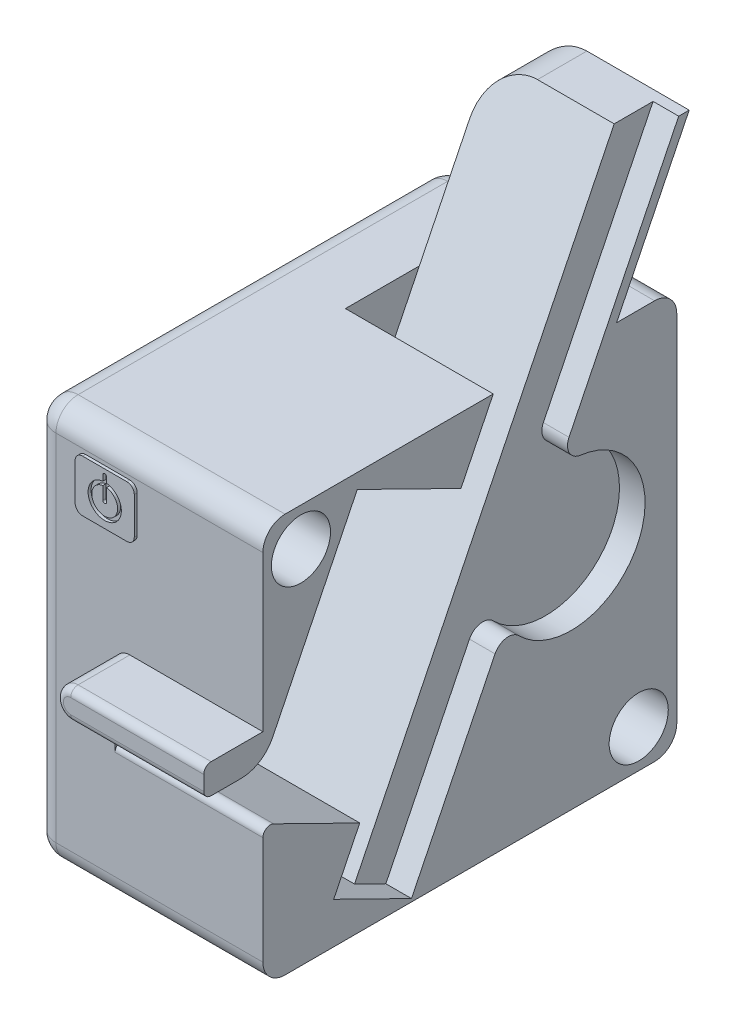
SolidWorks part; units mm, degrees
material "ABS"
ref_plane "Front" through (0, 0, 0) normal (0, 0, 1) x (1, 0, 0)
ref_plane "Top" through (0, 0, 0) normal (0, 1, 0) x (1, 0, 0)
ref_plane "Right" through (0, 0, 0) normal (1, 0, 0) x (0, 0, -1)
sketch "Sketch1" plane through (0, 0, 0) normal (0, 0, 1) x (1, 0, 0)
  line L0 (133.4483, 300.2587) -> (667.2416, 300.2587) construction
  line L2 (-196.85, 342.9) -> (196.85, 342.9)
  line L3 (-196.85, 342.9) -> (-196.85, 0)
  line L4 (-196.85, 0) -> (196.85, 0)
  line L5 (196.85, 342.9) -> (196.85, 0)
  dimension "D1" = 342.9
  dimension "D2" = 393.7
extrude "Boss-Extrude1" add sketch "Sketch1" along normal blind 355.6
sketch "Sketch2" plane through (0, 0, 355.6) normal (0, 0, 1) x (1, 0, 0)
  line L0 (196.85, 342.9) -> (-196.85, 342.9) construction
  line L1 (-158.75, 320.675) -> (-107.95, 320.675)
  line L2 (-158.75, 320.675) -> (-158.75, 276.225)
  line L3 (-158.75, 276.225) -> (-107.95, 276.225)
  line L4 (-107.95, 320.675) -> (-107.95, 276.225)
  line L5 (-158.75, 320.675) -> (-107.95, 276.225) construction
  line L6 (-158.75, 276.225) -> (-107.95, 320.675) construction
  line L7 (-196.85, 342.9) -> (-196.85, 0) construction
  point P0 (-133.35, 298.45)
  dimension "D1" = 44.45
  dimension "D2" = 63.5
  dimension "D3" = 44.45
  dimension "D4" = 50.8
extrude "Boss-Extrude2" add sketch "Sketch2" along normal blind 2.54
sketch "Sketch3" plane through (0, 0, 355.6) normal (0, 0, 1) x (1, 0, 0)
  line L0 (88.9, 298.45) -> (165.1, 298.45) construction
  line L1 (88.9, 307.975) -> (165.1, 307.975)
  line L2 (88.9, 288.925) -> (165.1, 288.925)
  line L5 (-107.95, 298.45) -> (88.9, 298.45) construction
  line L7 (-107.95, 276.225) -> (-107.95, 320.675) construction
  line L8 (196.85, 0) -> (196.85, 342.9) construction
  arc A0 (88.9, 307.975) -> (88.9, 288.925) centre (88.9, 298.45) ccw
  arc A1 (165.1, 288.925) -> (165.1, 307.975) centre (165.1, 298.45) ccw
  point P2 (127, 298.45)
  dimension "D1" = 19.05
  dimension "D2" = 76.2
  dimension "D3" = 31.75
extrude "Boss-Extrude3" add sketch "Sketch3" along normal blind 2.54
sketch "Sketch4" plane through (0, 0, 358.14) normal (0, 0, 1) x (1, 0, 0)
  line L0 (79.375, 298.45) -> (174.625, 298.45) construction
  arc A0 (88.9, 307.975) -> (88.9, 288.925) centre (88.9, 298.45) ccw construction
  arc A1 (165.1, 288.925) -> (165.1, 307.975) centre (165.1, 298.45) ccw construction
  circle A2 centre (92.075, 298.45) radius 3.81
  circle A3 centre (108.2865, 298.45) radius 3.81
  circle A4 centre (124.4979, 298.45) radius 3.81
  dimension "D1" = 7.62
  dimension "D2" = 16.2115
  dimension "D3" = 16.2115
  dimension "D4" = 12.7
extrude "Cut-Extrude1" cut sketch "Sketch4" against normal blind 2.54
sketch "Sketch5" plane through (0, 0, 355.6) normal (0, 0, 1) x (1, 0, 0)
  line L0 (-114.3, 177.8) -> (114.3, 177.8) construction
  line L1 (-114.3, 190.5) -> (114.3, 190.5)
  line L2 (-114.3, 165.1) -> (114.3, 165.1)
  line L3 (0, 177.8) -> (0, 342.9) construction
  line L4 (196.85, 342.9) -> (-196.85, 342.9) construction
  arc A0 (-114.3, 190.5) -> (-114.3, 165.1) centre (-114.3, 177.8) ccw
  arc A1 (114.3, 165.1) -> (114.3, 190.5) centre (114.3, 177.8) ccw
  point P2 (0, 177.8)
  dimension "D1" = 228.6
  dimension "D2" = 25.4
  dimension "D3" = 165.1
extrude "Boss-Extrude4" add sketch "Sketch5" along normal blind 50.8
fillet "Fillet1" radius 6.35 4 edges at (127, 177.8, 406.4) (0, 165.1, 406.4) (-127, 177.8, 406.4) (0, 190.5, 406.4)
fillet "Fillet2" radius 6.35 4 edges at (-158.75, 276.225, 356.87) (-107.95, 276.225, 356.87) (-107.95, 320.675, 356.87) (-158.75, 320.675, 356.87)
sketch "Sketch6" plane through (0, 0, 358.14) normal (0, 0, 1) x (1, 0, 0)
  line L0 (-133.35, 296.545) -> (-133.35, 276.225) construction
  line L3 (-133.35, 296.545) -> (-133.35, 315.595) construction
  line L4 (-134.9375, 296.545) -> (-134.9375, 315.595)
  line L5 (-131.7625, 296.545) -> (-131.7625, 315.595)
  line L6 (-152.4, 276.225) -> (-114.3, 276.225) construction
  circle A1 centre (-133.35, 296.545) radius 11.1125
  circle A2 centre (-133.35, 296.545) radius 14.2875
  arc A3 (-134.9375, 296.545) -> (-131.7625, 296.545) centre (-133.35, 296.545) ccw
  arc A4 (-131.7625, 315.595) -> (-134.9375, 315.595) centre (-133.35, 315.595) ccw
  point P12 (-133.35, 306.07)
  dimension "D2" = 22.225
  dimension "D3" = 3.175
  dimension "D4" = 19.05
  dimension "D5" = 20.32
  dimension "D1" = 3.175
extrude "Cut-Extrude2" cut sketch "Sketch6" against normal blind 2.54 contours L4 A2 L5 A1 | L5 A4 L4 A2 | L5 A2 L4 A1 | L4 A3 L5 A1 region at (-133.35, 301.4538, 358.14) region at (-140.889, 287.8397, 358.14) region at (-133.35, 309.2112, 358.14) region at (-133.35, 313.8328, 358.14)
fillet "Fillet3" radius 19.05 12 edges at (-196.85, 171.45, 0) (-196.85, 171.45, 355.6) (196.85, 171.45, 0) (196.85, 171.45, 355.6) (0, 0, 0) (0, 0, 355.6) (0, 342.9, 0) (0, 342.9, 355.6) (-196.85, 342.9, 177.8) (196.85, 0, 177.8) (-196.85, 0, 177.8) (196.85, 342.9, 177.8)
sketch "Sketch7" plane through (0, 0, 0) normal (1, 0, 0) x (0, 0, -1)
  line L0 (-51.7276, 342.9) -> (10.6627, 469.9)
  line L1 (-336.55, 342.9) -> (-19.05, 342.9) construction
  line L2 (-94.1768, 342.9) -> (-31.7865, 469.9)
  line L3 (-31.7865, 469.9) -> (10.6627, 469.9)
  line L4 (-94.1768, 342.9) -> (-51.7276, 342.9)
  line L5 (0, 323.85) -> (0, 19.05) construction
  dimension "D1" = 38.1
  dimension "D2" = 127
  dimension "D3" = 94.1768
  dimension "D4" = 63.837
extrude "Boss-Extrude5" add sketch "Sketch7" along normal mid plane 254
fillet "Fillet4" radius 39.116 2 edges at (-127, 469.9, 10.5619) (127, 469.9, 10.5619)
sketch "Sketch8" plane through (0, 342.9, 0) normal (0, 1, 0) x (1, 0, 0)
  line L0 (0, -94.1768) -> (0, -125.9268) construction
  line L1 (127, -94.1768) -> (-127, -94.1768) construction
  line L3 (-127, -157.6768) -> (127, -157.6768)
  line L4 (-127, -157.6768) -> (-127, -94.1768)
  line L5 (-127, -94.1768) -> (127, -94.1768)
  line L6 (127, -157.6768) -> (127, -94.1768)
  line L7 (-127, -157.6768) -> (127, -94.1768) construction
  line L8 (-127, -94.1768) -> (127, -157.6768) construction
  dimension "D1" = 63.5
  dimension "D2" = 254
extrude "Cut-Extrude3" cut sketch "Sketch8" against normal blind 25.4
sketch "Sketch9" plane through (0, 0, 0) normal (1, 0, 0) x (0, 0, -1)
  line L1 (-912.7094, 769.4471) -> (-210.006, -1175.153)
  line L2 (-210.006, -1175.153) -> (1122.7154, 405.706)
  line L3 (1122.7154, 405.706) -> (-912.7094, 769.4471)
  circle A0 centre (0, 0) radius 596.8851 construction
extrude "Cut-Extrude4" cut sketch "Sketch9" along normal through all
sketch "Sketch10" plane through (0, 0, 0) normal (1, 0, 0) x (0, 0, -1)
  line L0 (-94.1768, 342.9) -> (-254.8643, 15.8091)
  line L1 (-157.6768, 342.9) -> (-185.414, 286.439)
  line L2 (-31.7865, 469.9) -> (-94.1768, 342.9) construction
  line L3 (-355.6, 165.1) -> (-274.4926, 330.2)
  line L5 (-355.6, 19.05) -> (-355.6, 165.1) construction
  line L7 (-355.6, 165.1) -> (-355.6, 121.8957)
  line L9 (-157.6768, 342.9) -> (-94.1768, 342.9)
  line L14 (-274.4926, 330.2) -> (-185.414, 286.439)
  line L15 (-355.6, 121.8957) -> (-268.5142, 299.1651) construction
  line L16 (-157.6768, 342.9) -> (-336.55, 342.9) construction
  line L17 (-355.6, 121.8957) -> (-272.3609, 81.0035)
  line L19 (-254.8643, 15.8091) -> (-294.7601, 35.4084)
  line L20 (-294.7601, 35.4084) -> (-272.3609, 81.0035)
  dimension "D1" = 19.05
  dimension "D2" = 12.7
  dimension "D3" = 50.8
  dimension "D4" = 44.45
extrude "Cut-Extrude5" cut sketch "Sketch10" against normal blind 127
sketch "Sketch11" plane through (0, 0, 0) normal (1, 0, 0) x (0, 0, -1)
  line L0 (-94.1768, 342.9) -> (-106.6549, 317.5)
  line L1 (-106.6549, 317.5) -> (-94.1768, 317.5)
  line L2 (-94.1768, 317.5) -> (-94.1768, 342.9)
extrude "Boss-Extrude6" add sketch "Sketch11" against normal up to surface (127 mm away) up to face at (-127, 214.2414, 222.3434)
sketch "Sketch12" plane through (0, 103.9367, 211.5706) normal (0, 0.4409, 0.8975) x (1, 0, 0)
  line L0 (-127, -98.1877) -> (0, -98.1877) construction
  line L1 (0, 426.4566) -> (-22, 426.4566)
  line L2 (0, 426.4566) -> (0, -98.1877)
  line L3 (0, -98.1877) -> (-22, -98.1877)
  line L4 (-22, 426.4566) -> (-22, -98.1877)
  dimension "D1" = 22
extrude "Cut-Extrude6" cut sketch "Sketch12" against normal blind 30
sketch "Sketch13" plane through (0, 0, 0) normal (1, 0, 0) x (0, 0, -1)
  line L0 (-90.7362, 196.8695) -> (0, 196.8695) construction
  line L1 (0, 19.05) -> (0, 323.85) construction
  line L2 (-90.7362, 196.8695) -> (-90.7362, 0) construction
  line L3 (-336.55, 0) -> (-19.05, 0) construction
  circle A0 centre (-90.7362, 196.8695) radius 63.5
  dimension "D3" = 127
  dimension "D1" = 196.8695
  dimension "D2" = 90.7362
extrude "Cut-Extrude7" cut sketch "Sketch13" against normal up to surface (22 mm away) up to face at (-22, 239.5476, 128.2377)
fillet "Fillet5" radius 12.7 2 edges at (-11, 259.4033, 101.771) (-11, 167.3852, 146.9761)
sketch "Sketch14" plane through (0, 0, 0) normal (1, 0, 0) x (0, 0, -1)
  line L0 (-400.05, 165.1) -> (-355.6, 165.1) construction
  line L1 (-274.4926, 330.2) -> (-355.6, 165.1) construction
  line L2 (-274.4926, 330.2) -> (-355.6, 165.1) construction
  line L3 (-374.5857, 165.1) -> (-355.6, 165.1)
  line L4 (-355.6, 165.1) -> (-347.2286, 182.1405)
  arc A0 (-374.5857, 165.1) -> (-347.2286, 182.1405) centre (-374.5857, 195.58) ccw
  dimension "D1" = 30.48
extrude "Cut-Extrude8" cut sketch "Sketch14" against normal up to surface (127 mm away) up to face at (-127, 191.2951, 249.4384)
fillet "Fillet7" radius 6.35 1 edges at (-63.5, 121.8957, 355.6)
sketch "Sketch15" plane through (0, 0, 0) normal (1, 0, 0) x (0, 0, -1)
  circle A0 centre (-322.9044, 310.2044) radius 25.4
  circle A1 centre (-32.6956, 32.6956) radius 25.4
  dimension "D1" = 50.8
  dimension "D2" = 50.8
extrude "Cut-Extrude9" cut sketch "Sketch15" against normal blind 53.34
equation "\"D3@Sketch4\"=\"D2@Sketch4\""
